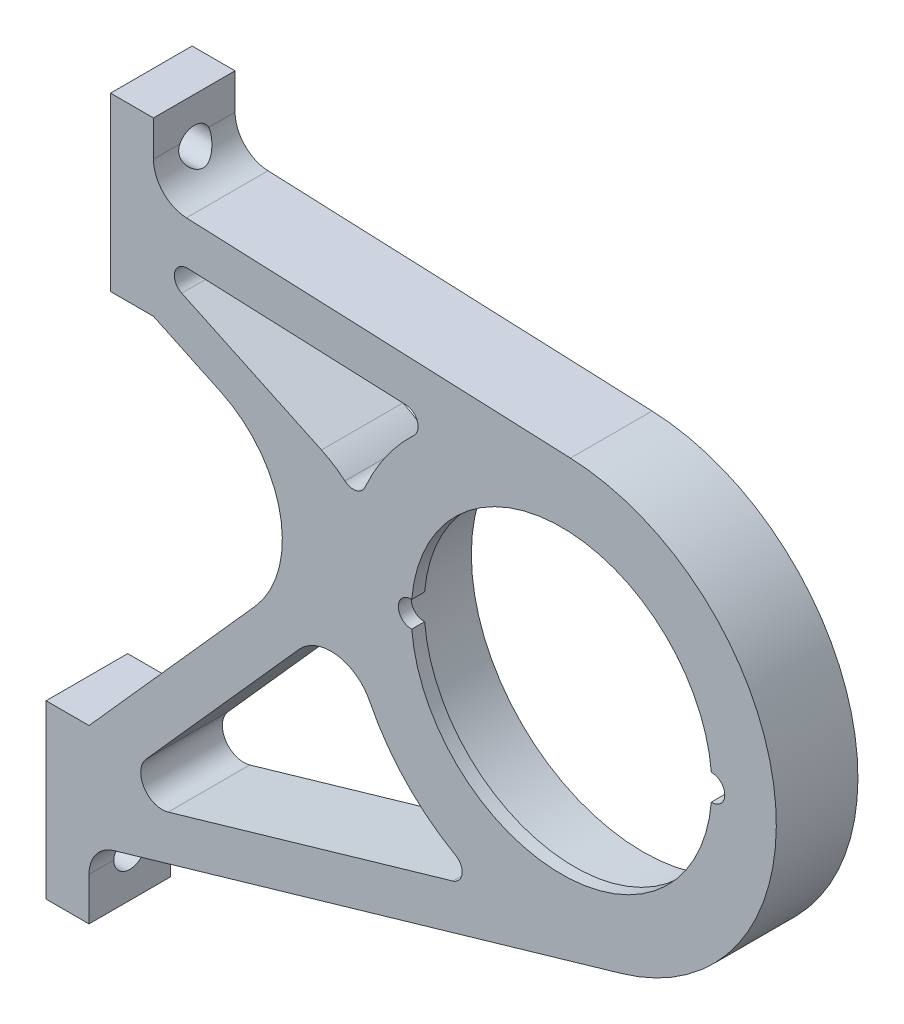
SolidWorks part; units mm, degrees
material "6061 Alloy"
ref_plane "Front Plane" through (0, 0, 0) normal (0, 0, 1) x (1, 0, 0)
ref_plane "Top Plane" through (0, 0, 0) normal (0, 1, 0) x (1, 0, 0)
ref_plane "Right Plane" through (0, 0, 0) normal (1, 0, 0) x (0, 0, -1)
sketch "Sketch1" plane through (0, 0, 0) normal (0, 0, 1) x (1, 0, 0)
  line L0 (-133.35, 88.9) -> (-133.35, 38.1)
  line L1 (-133.35, 38.1) -> (-120.65, 38.1)
  line L2 (-133.35, 88.9) -> (-120.65, 88.9)
  line L3 (-120.65, 88.9) -> (-120.65, 68.58)
  line L4 (-120.65, 68.58) -> (2.6424, 63.445)
  line L5 (-152.4, -76.2) -> (-139.7, -76.2)
  line L6 (-152.4, -76.2) -> (-152.4, -127)
  line L7 (-152.4, -127) -> (-139.7, -127)
  line L8 (-139.7, -127) -> (-139.7, -106.68)
  line L9 (-139.7, -106.68) -> (17.7044, -60.982)
  line L10 (-120.65, 38.1) -> (-100.7551, 28.7158)
  line L11 (-139.7, -76.2) -> (-90.6011, -21.1288)
  line L12 (-46.0374, 52.7615) -> (-110.4951, 55.4461)
  line L13 (-112.2791, 48.1935) -> (-70.9856, 28.7158)
  line L14 (-77.621, -25.6539) -> (-122.808, -76.3375)
  line L15 (-116.2978, -86.6614) -> (-32.1185, -62.2223)
  arc A0 (-56.7845, -28.4212) -> (-31.3026, -55.2485) centre (0, 0) ccw
  circle A1 centre (0, 0) radius 50.8
  arc A2 (-90.6011, -21.1288) -> (-100.7551, 28.7158) centre (-114.3, 0) ccw
  arc A3 (-64.0429, 24.2554) -> (-70.9856, 28.7158) centre (-84.5305, 0) ccw
  arc A4 (-110.4951, 55.4461) -> (-112.2791, 48.1935) centre (-110.6537, 51.6394) ccw
  arc A6 (-122.808, -76.3375) -> (-116.2978, -86.6614) centre (-118.0683, -80.5632) ccw
  arc A7 (17.7044, -60.982) -> (2.6424, 63.445) centre (0, 0) ccw
  arc A8 (-43.5811, 46.1837) -> (-58.0985, 25.6283) centre (0, 0) ccw
  arc A9 (-46.0374, 52.7615) -> (-43.5811, 46.1837) centre (-46.196, 48.9548) cw
  arc A10 (-64.0429, 24.2554) -> (-58.0985, 25.6283) centre (-61.5844, 27.166) ccw
  arc A11 (-32.1185, -62.2223) -> (-31.3026, -55.2485) centre (-33.1808, -58.5634) ccw
  arc A12 (-77.621, -25.6539) -> (-56.7845, -28.4212) centre (-68.1415, -34.1055) cw
  point P44 (-35.9531, 52.3414)
  dimension "D1" = 12.7
  dimension "D2" = 101.6
  dimension "D13" = 63.5
  dimension "D14" = 31.75
  dimension "D17" = 3.81
  dimension "D18" = 31.75
  dimension "D21" = 6.35
  dimension "D22" = 3.81
  dimension "D23" = 3.81
  dimension "D24" = 12.7
  dimension "D3" = 50.8
  dimension "D4" = 12.7
  dimension "D5" = 20.32
  dimension "D6" = 133.35
  dimension "D7" = 152.4
  dimension "D8" = 12.7
  dimension "D9" = 50.8
  dimension "D10" = 20.32
  dimension "D11" = 88.9
  dimension "D12" = 127
  dimension "D15" = 12.7
  dimension "D16" = 12.7
  dimension "D19" = 12.7
  dimension "D20" = 12.7
extrude "Boss-Extrude1" add sketch "Sketch1" along normal blind 24.13
fillet "Fillet1" radius 10.16 2 edges at (-139.7, -106.68, 12.065) (-120.65, 68.58, 12.065)
sketch "Sketch2" plane through (-152.4, 0, 0) normal (-1, 0, 0) x (0, 0, 1)
  line L0 (24.13, 88.9) -> (0, 88.9) construction
  line L1 (24.13, -127) -> (0, -127) construction
  circle A0 centre (12.065, -114.3) radius 4.7625
  circle A1 centre (12.065, 76.2) radius 4.7625
  point P6 (12.065, 88.9)
  dimension "D1" = 9.525
  dimension "D2" = 12.7
  dimension "D3" = 12.7
extrude "Cut-Extrude1" cut sketch "Sketch2" against normal through all
sketch "Sketch3" plane through (0, 0, 24.13) normal (0, 0, 1) x (1, 0, 0)
  arc A0 (-44.2867, -3.8065) -> (44.2867, -3.8065) centre (0, 0) ccw
  arc A1 (-44.2867, 3.8065) -> (-44.2867, -3.8065) centre (-44.45, 0) ccw
  circle A2 centre (0, 0) radius 50.8 construction
  circle A3 centre (0, 0) radius 50.8
  arc A4 (44.2867, -3.8065) -> (44.2867, 3.8065) centre (44.45, 0) ccw
  arc A5 (44.2867, 3.8065) -> (-44.2867, 3.8065) centre (0, 0) ccw
  point P4 (0, 0)
  point P9 (0, 0)
  point P10 (0, 0)
  circle M24 centre (0, 0) radius 50.8
  dimension "D1" = 88.9
  dimension "D2" = 2.54
  dimension "D3" = 2.54
extrude "Boss-Extrude2" add sketch "Sketch3" against normal blind 3.81 contours A5 A4 A1 M24 | A4 A0 A1 A3 region at (-49.3632, 0, 24.13)
